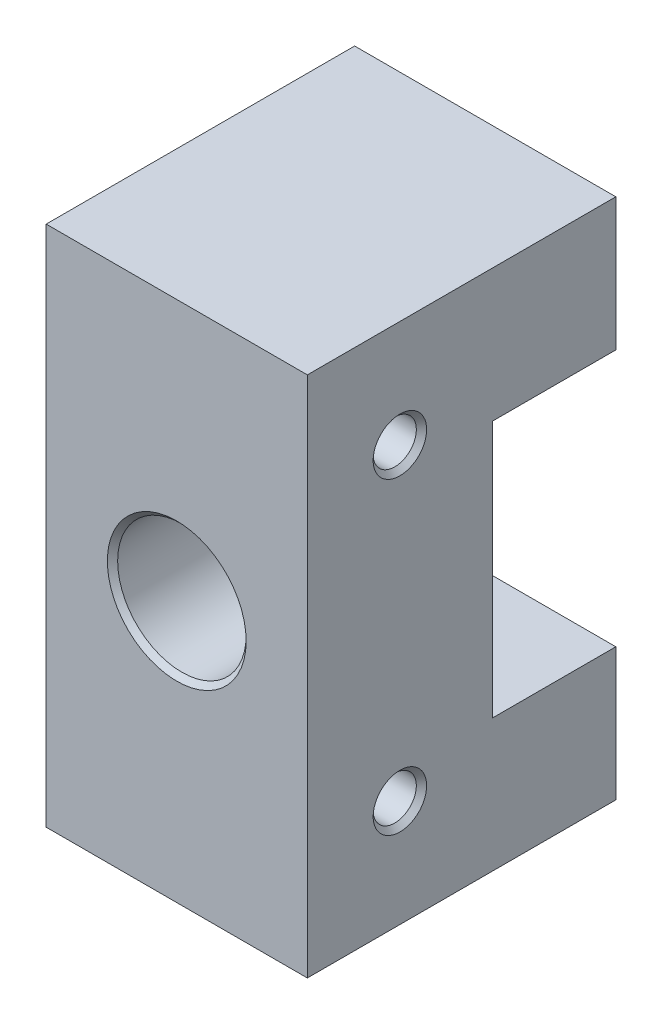
SolidWorks part; units mm, degrees
material "6061 Alloy"
ref_plane "Front Plane" through (0, 0, 0) normal (0, 0, 1) x (1, 0, 0)
ref_plane "Top Plane" through (0, 0, 0) normal (0, 1, 0) x (1, 0, 0)
ref_plane "Right Plane" through (0, 0, 0) normal (1, 0, 0) x (0, 0, -1)
sketch "Sketch1" plane through (0, 0, 0) normal (0, 0, 1) x (1, 0, 0)
  line L1 (-12.7, 25.4) -> (12.7, 25.4)
  line L2 (-12.7, 25.4) -> (-12.7, -25.4)
  line L3 (-12.7, -25.4) -> (12.7, -25.4)
  line L4 (12.7, 25.4) -> (12.7, -25.4)
  line L5 (-12.7, 25.4) -> (12.7, -25.4) construction
  line L6 (-12.7, -25.4) -> (12.7, 25.4) construction
  point P0 (0, 0)
  dimension "D1" = 50.8
  dimension "D2" = 25.4
extrude "Boss-Extrude1" add sketch "Sketch1" along normal blind 30
sketch "Sketch2" plane through (0, 0, 0) normal (0, 0, 1) x (1, 0, 0)
  line L0 (-12.7, 25.4) -> (-12.7, -25.4) construction
  line L1 (12.7, 12.5) -> (-12.7, 12.5)
  line L2 (12.7, 12.5) -> (12.7, -12.5)
  line L3 (12.7, -12.5) -> (-12.7, -12.5)
  line L4 (-12.7, 12.5) -> (-12.7, -12.5)
  line L5 (12.7, 12.5) -> (-12.7, -12.5) construction
  line L6 (12.7, -12.5) -> (-12.7, 12.5) construction
  point P0 (0, 0)
  dimension "D1" = 25
extrude "Cut-Extrude1" cut sketch "Sketch2" along normal blind 12
hole_wizard "M12 Clearance Hole1" positions "Sketch7" profile "Sketch8" hole size "M12" standard "ANSI Metric" end condition up to next
sketch "Sketch7" plane through (0, 0, 12) normal (0, 0, -1) x (-1, 0, 0)
  point P0 (0, 0)
sketch "Sketch8" plane through (0, 0, 12) normal (1, 0, 0) x (0, 1, 0)
  line L0 (0, 0) -> (0, 18)
  line L1 (0, 18) -> (6.25, 18)
  line L2 (6.25, 18) -> (6.25, 0)
  line L5 (6.25, 0) -> (0, 0)
  line L11 (0, -6.35) -> (0, 107.95) construction
  dimension "Thru Hole Dia." = 12.5
  dimension "Thru Hole Depth" = 18
hole_wizard "M5x0.8 Tapped Hole1" positions "Sketch10" profile "Sketch11" tap size "M5x0.8" standard "ANSI Metric"
sketch "Sketch10" plane through (12.7, 0, 0) normal (1, 0, 0) x (0, 0, -1)
  line L0 (-21, 15) -> (-21, -15) construction
  line L2 (-30, 0) -> (-12, 0) construction
  line L3 (-30, -25.4) -> (-30, 25.4) construction
  line L4 (-12, -12.5) -> (-12, 12.5) construction
  point P0 (-21, 15)
  point P2 (-21, -15)
  point P16 (-21, 0)
  dimension "D1" = 30
sketch "Sketch11" plane through (12.7, 15, 21) normal (0, 1, 0) x (0, 0, -1)
  line L0 (0, 0) -> (0, 12)
  line L1 (0, 12) -> (2.1, 10.7382)
  line L2 (2.1, 10.7382) -> (2.1, 0)
  line L5 (2.1, 0) -> (0, 0)
  line L10 (0, 12) -> (-2.1, 10.7382) construction
  line L11 (0, -6.35) -> (0, 107.95) construction
  dimension "Tap Drill Dia." = 4.2
  dimension "Tap Drill Depth" = 12
  dimension "Drill Angle" = 118
cosmetic thread "Hole Thread5" parameters "D1"=10, "D2"=5
cosmetic thread "Hole Thread6" parameters "D1"=10, "D2"=5
mirror "Mirror1" about plane through (0, 0, 0) normal (1, 0, 0) of "M5x0.8 Tapped Hole1"
cosmetic thread "Hole Thread7" parameters "D1"=10, "D2"=5
cosmetic thread "Hole Thread8" parameters "D1"=10, "D2"=5
chamfer "Chamfer1 0.5 mm" distance 0.5 angle 45 6 edges at (6.25, 0, 30) (-6.25, 0, 12) (12.7, -15, 18.9) (12.7, 15, 18.9) (-12.7, -15, 23.1) (-12.7, 15, 23.1)
equation "\"D1@Sketch1\"=2in"
